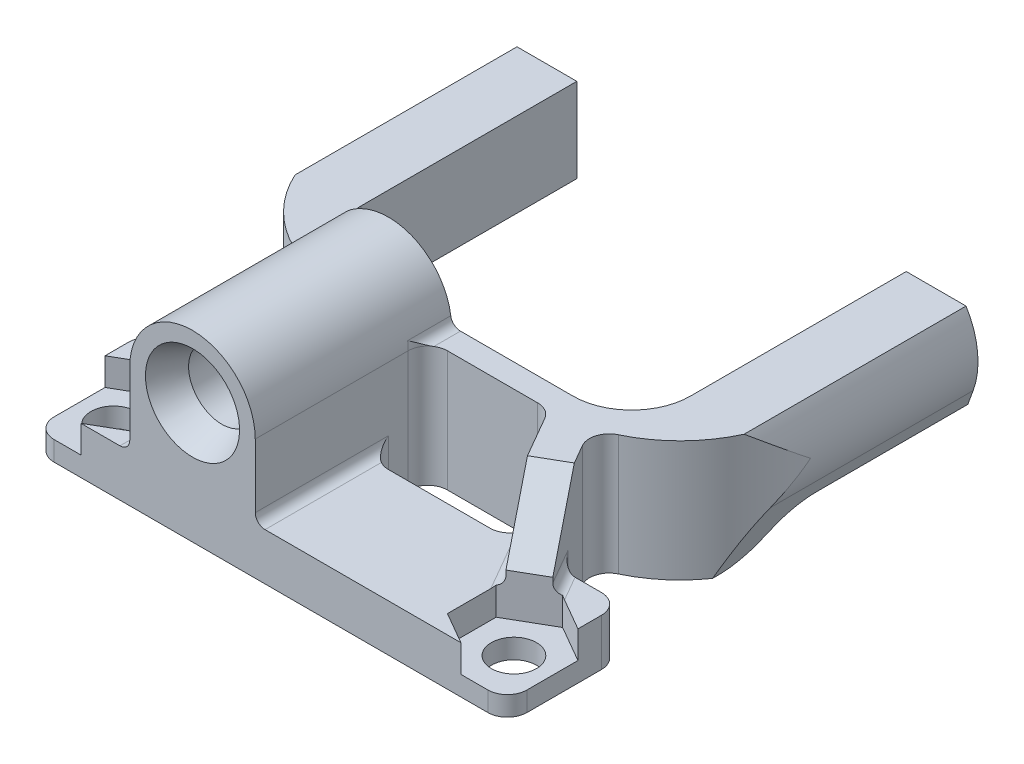
SolidWorks part; units mm, degrees
material "ABS"
ref_plane "Front Plane" through (0, 0, 0) normal (0, 0, 1) x (1, 0, 0)
ref_plane "Top Plane" through (0, 0, 0) normal (0, 1, 0) x (1, 0, 0)
ref_plane "Right Plane" through (0, 0, 0) normal (1, 0, 0) x (0, 0, -1)
sketch "Sketch1" plane through (0, 0, 0) normal (0, 0, 1) x (1, 0, 0)
  line L0 (-7.96, -4.1) -> (7.96, -4.1) construction
  line L5 (-11.4511, 2.15) -> (-7.2, 2.15)
  line L19 (-9.675, 0) -> (9.675, 0) construction
  line L20 (-0.8, 2.15) -> (11.4511, 2.15)
  line L22 (8.86, -4) -> (-8.86, -4)
  line L23 (11.8127, -1.4023) -> (10.8672, -4)
  line L24 (-11.8127, -1.4023) -> (-10.8672, -4)
  line L25 (-10.8672, -4) -> (-8.86, -4)
  line L26 (8.86, -4) -> (10.8672, -4)
  circle A0 centre (-9.675, 0) radius 0.6 construction
  circle A4 centre (9.675, 0) radius 0.6 construction
  arc A6 (-11.4511, 2.15) -> (-11.8127, -1.4023) centre (-7.96, 0) ccw
  arc A7 (11.4511, 2.15) -> (11.8127, -1.4023) centre (7.96, 0) cw
  arc A9 (-0.8, 2.15) -> (-7.2, 2.15) centre (-4, 2.15) ccw
  arc A10 (8.86, -4) -> (7.96, -4.1) centre (7.96, 0) cw construction
  arc A11 (-8.86, -4) -> (-7.96, -4.1) centre (-7.96, 0) ccw construction
  dimension "D3" = 1.2
  dimension "D5" = 4.1
  dimension "D8" = 70
  dimension "D9" = 3.2
  dimension "D7" = 4
  dimension "D12" = 2.15
  dimension "D2" = 9.675
  dimension "D4" = 1.715
  dimension "D6" = 1.715
  dimension "D10" = 70
  dimension "D11" = 2.15
  dimension "D13" = 4
extrude "Boss-Extrude2" add sketch "Sketch1" against normal blind 24
sketch "Sketch3" plane through (0, 0, 0) normal (0, 1, 0) x (1, 0, 0)
  line L0 (-8.4, 24) -> (8.4, 24)
  line L1 (8.4, 24) -> (8.4, 13)
  line L2 (5.4, 10) -> (-5.4, 10)
  line L3 (-8.4, 13) -> (-8.4, 24)
  line L4 (11.4511, 24) -> (-0.8, 24) construction
  line L5 (-0.8, 0) -> (12.06, 0)
  line L6 (12.06, 0) -> (12.06, 15.46)
  line L7 (12.06, 0) -> (12.06, 24) construction
  line L8 (-0.8, 0) -> (-0.8, 8.8)
  line L9 (-0.8, 24) -> (-0.8, 0) construction
  line L10 (-0.8, 8.8) -> (5.4, 8.8)
  line L11 (5.4, 8.8) -> (5.4, 10) construction
  line L12 (-7.2, 0) -> (-12.06, 0)
  line L13 (-12.06, 0) -> (-12.06, 15.46)
  line L14 (-12.06, 24) -> (-12.06, 0) construction
  line L15 (-5.4, 10) -> (-5.4, 8.8) construction
  line L16 (-7.2, 0) -> (-7.2, 9.0479)
  line L17 (-7.2, 24) -> (-7.2, 0) construction
  arc A0 (-5.4, 10) -> (-8.4, 13) centre (-5.4, 13) cw
  arc A1 (8.4, 13) -> (5.4, 10) centre (5.4, 13) cw
  arc A2 (5.4, 8.8) -> (12.06, 15.46) centre (5.4, 15.46) ccw
  arc A3 (-7.2, 9.0479) -> (-12.06, 15.46) centre (-5.4, 15.46) cw
  arc A4 (-5.4, 8.8) -> (-7.2, 9.0479) centre (-5.4, 15.46) cw construction
  dimension "D4" = 3
  dimension "D1" = 8.4
  dimension "D2" = 14
  dimension "D3" = 8.4
  dimension "D5" = 1.2
extrude "Cut-Extrude2" cut sketch "Sketch3" against normal through all both and the other way through all
sketch "Sketch4" plane through (0, 0, 0) normal (0, 0, 1) x (1, 0, 0)
  line L0 (-4, 2.15) -> (-4, 0) construction
  line L1 (-4, 0) -> (0, 0) construction
  circle A0 centre (-4, 2.15) radius 1.7
  dimension "D1" = 3.4
  dimension "D2" = 2.15
  dimension "D3" = 4
extrude "Cut-Extrude3" cut sketch "Sketch4" against normal through all
chamfer "Chamfer1" distance 1.5 angle 25 1 edges at (-2.3, 2.15, 0) first distance on face at (-2.3, 2.15, 0)
sketch "Sketch10" plane through (0, 0, 0) normal (0, 1, 0) x (1, 0, 0)
  line L0 (-4, -7.1251) -> (-4, 25.7113) construction
  line L1 (-4, 7.2) -> (-6.5, 8.3658)
  line L3 (-4, 12.2) -> (-4, 7.2)
  line L4 (-11.4511, 24) -> (-12.06, 24) construction
  line L7 (-6.5, 8.3658) -> (-6.5, 12.2)
  line L8 (-6.5, 12.2) -> (-4, 12.2)
  dimension "D1" = 4
  dimension "D2" = 16.8
  dimension "D3" = 65
  dimension "D4" = 5
  dimension "D5" = 5
revolve "Cut-Revolve2" cut sketch "Sketch10" angle 360 about L0
sketch "Sketch6" plane through (0, 0, -24) normal (0, 0, -1) x (-1, 0, 0)
  line L0 (-9.675, 0) -> (9.675, 0) construction
  circle A0 centre (-9.675, 0) radius 0.8
  circle A1 centre (9.675, 0) radius 0.8
  dimension "D1" = 1.6
  dimension "D2" = 19.35
extrude "Cut-Extrude5" cut sketch "Sketch6" against normal blind 6
sketch "Sketch7" plane through (0, 0, 0) normal (0, 0, 1) x (1, 0, 0)
  line L0 (-12.06, -1.6) -> (-12.06, -4)
  line L2 (-12.06, -4) -> (12.06, -4)
  line L3 (12.06, -4) -> (12.06, -1.6)
  line L6 (-7.2, -4) -> (-0.8, -4) construction
  line L7 (-12.06, -1.6) -> (12.06, -1.6)
  line L9 (12.06, -1.6) -> (12.06, 0) construction
  line L10 (-12.06, 0) -> (-12.06, -1.6) construction
  arc A0 (-7.06, -4) -> (-11.4511, 2.15) centre (-7.96, 0) ccw construction
  arc A1 (4.4689, 2.15) -> (8.86, -4) centre (7.96, 0) ccw construction
  dimension "D1" = 2.4
extrude "Boss-Extrude3" add sketch "Sketch7" against normal blind 5.8
sketch "Sketch8" plane through (0, -4, 0) normal (0, 1, 0) x (1, 0, 0)
  line L1 (-10.21, -0.3) -> (-8.06, 0.9413)
  line L2 (-8.06, 0.9413) -> (-8.06, 3.4239)
  line L3 (-8.06, 3.4239) -> (-10.21, 4.6652)
  line L4 (-10.21, 4.6652) -> (-12.36, 3.4239)
  line L5 (-12.36, 3.4239) -> (-12.36, 0.9413)
  line L6 (-12.36, 0.9413) -> (-10.21, -0.3) construction
  line L7 (10.21, -0.3) -> (12.36, 0.9413) construction
  line L8 (12.36, 0.9413) -> (12.36, 3.4239)
  line L9 (12.36, 3.4239) -> (10.21, 4.6652)
  line L10 (10.21, 4.6652) -> (8.06, 3.4239)
  line L11 (8.06, 3.4239) -> (8.06, 0.9413)
  line L12 (8.06, 0.9413) -> (10.21, -0.3)
  line L13 (-10.21, 2.1826) -> (10.21, 2.1826) construction
  line L14 (0, 2.1826) -> (0, 0) construction
  line L15 (-12.06, 0) -> (-3.86, 0) construction
  line L16 (-12.36, 0.9413) -> (-12.36, -0.3)
  line L17 (-12.36, -0.3) -> (-10.21, -0.3)
  line L18 (10.21, -0.3) -> (12.36, -0.3)
  line L19 (12.36, -0.3) -> (12.36, 0.9413)
  line L20 (-12.06, 5.8) -> (-12.06, 0) construction
  circle A0 centre (-10.21, 2.1826) radius 2.15 construction
  circle A1 centre (10.21, 2.1826) radius 2.15 construction
  dimension "D1" = 4.3
  dimension "D2" = 0.3
  dimension "D3" = 0.3
extrude "Cut-Extrude6" cut sketch "Sketch8" along normal up to next from offset 1
sketch "Sketch9" plane through (0, -4, 0) normal (0, -1, 0) x (1, 0, 0)
  circle A0 centre (10.21, -2.1826) radius 1.15
  circle A1 centre (-10.21, -2.1826) radius 1.15
  dimension "D1" = 2.3
extrude "Cut-Extrude7" cut sketch "Sketch9" against normal up to next
sketch "Sketch11" plane through (0, 0, 0) normal (1, 0, 0) x (0, 0, -1)
  line L0 (24, -4) -> (24, -2.15)
  line L1 (24, -2.15) -> (15.2047, -2.15)
  line L2 (15.2047, -2.15) -> (13, -4)
  line L3 (13, -4) -> (24, -4)
  line L4 (24, -4) -> (11.6567, -4) construction
  line L5 (24, -4) -> (24, -1.4023) construction
  dimension "D1" = 1.85
  dimension "D2" = 11
  dimension "D4" = 40
extrude "Cut-Extrude8" cut sketch "Sketch11" against normal through all both and the other way through all
sketch "Sketch15" plane through (0, -4, 0) normal (0, 1, 0) x (1, 0, 0)
  line L0 (9.8928, 4.4821) -> (6.7928, 9.8514)
  line L1 (6.7928, 9.8514) -> (5.2772, 8.9764)
  line L2 (5.2772, 8.9764) -> (8.3772, 3.6071)
  line L3 (12.06, 5.8) -> (-0.8, 5.8) construction
  line L4 (-9.8928, 4.4821) -> (-6.7928, 9.8514)
  line L5 (-6.7928, 9.8514) -> (-5.2772, 8.9764)
  line L6 (-5.2772, 8.9764) -> (-8.3772, 3.6071)
  line L7 (-7.2, 5.8) -> (-12.06, 5.8) construction
  line L8 (-8.3772, 3.6071) -> (-9.8928, 4.4821)
  line L9 (9.8928, 4.4821) -> (8.3772, 3.6071)
  line L10 (10.21, 4.6652) -> (8.06, 3.4239) construction
  line L11 (-8.06, 3.4239) -> (-10.21, 4.6652) construction
  line L12 (-10.21, 2.1826) -> (-9.135, 4.0446) construction
  line L13 (10.21, 2.1826) -> (9.135, 4.0446) construction
  dimension "D1" = 60
  dimension "D2" = 60
  dimension "D3" = 1.75
  dimension "D4" = 6.2
extrude "Boss-Extrude4" add sketch "Sketch15" along normal up to surface (6.15 mm away) up to face at (6.2614, 2.15, -13.7213)
other "DeleteFace1" face at (-5.5591, 2.15, -8.8137) face at (-5.7368, 0.9766, -9.2418) face at (-5.5454, 0.3982, -8.5119) and patch yes
chamfer "Chamfer2" distance 3 angle 45 2 edges at (9.135, 2.15, -4.0446) (-9.135, 2.15, -4.0446)
fillet "Fillet8" radius 0.5 9 edges at (-0.8, -1.6, -2.9) (-7.2, -1.6, -2.823) (-7.2, 2.15, -8.4957) (-0.8, 2.15, -9.4) (9.5123, -1.6, -5.141) (7.7442, -1.6, -4.7035) (-9.5123, -1.6, -5.141) (-7.7886, -1.6, -4.6266) (-7.2, -0.0478, -5.6461)
fillet "Fillet7" radius 1 13 edges at (-12.06, -3.5, 0) (12.06, -3.5, 0) (12.06, -2.8, -5.8) (-12.06, -2.8, -5.8) (7.1111, -2.55, -5.8) (-0.8, -2.55, -5.8) (7.2487, -0.925, -9.0617) (-0.8, -0.925, -8.8) (5.3791, -0.925, -8.8) (-7.2487, -0.8127, -9.0617) (-0.8073, 2.3667, -8.8) (-9.1319, -2.55, -5.8) (9.1319, -2.55, -5.8)
fillet "Fillet10" radius 3 4 edges at (9.6336, -4, -13) (-9.6336, -4, -13) (-9.9703, -2.15, -15.2047) (9.9703, -2.15, -15.2047)
